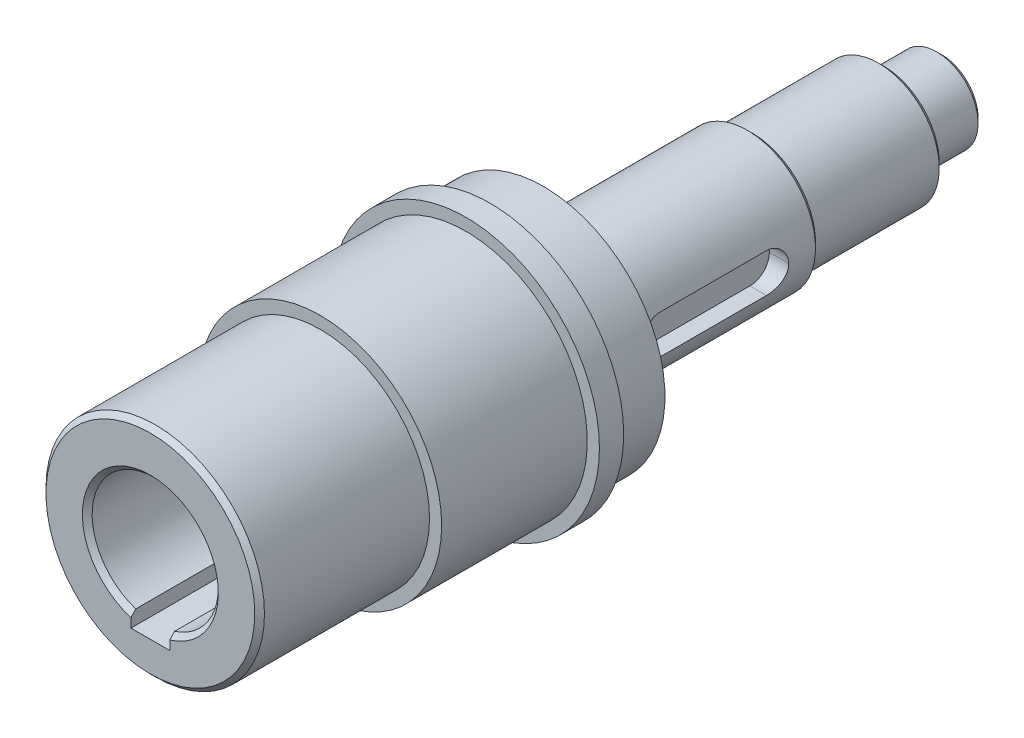
SolidWorks part; units mm, degrees
ref_plane "前视基准面" through (0, 0, 0) normal (0, 0, 1) x (1, 0, 0)
ref_plane "上视基准面" through (0, 0, 0) normal (0, 1, 0) x (1, 0, 0)
ref_plane "右视基准面" through (0, 0, 0) normal (1, 0, 0) x (0, 0, -1)
sketch "草图1" plane through (0, 0, 0) normal (0, 0, 1) x (1, 0, 0)
  circle A0 centre (0, 0) radius 25
  dimension "D1" = 50
extrude "凸台-拉伸1" add sketch "草图1" along normal blind 30
sketch "草图2" plane through (0, 0, 0) normal (0, 0, -1) x (-1, 0, 0)
  circle A0 centre (0, 0) radius 27.5
  dimension "D1" = 55
extrude "凸台-拉伸2" add sketch "草图2" along normal blind 5
sketch "草图3" plane through (0, 0, -5) normal (0, 0, -1) x (-1, 0, 0)
  circle A0 centre (0, 0) radius 25
  dimension "D1" = 50
extrude "凸台-拉伸3" add sketch "草图3" along normal blind 11
sketch "草图4" plane through (0, 0, -16) normal (0, 0, -1) x (-1, 0, 0)
  circle A0 centre (0, 0) radius 14
  dimension "D1" = 28
extrude "凸台-拉伸4" add sketch "草图4" along normal blind 43
sketch "草图5" plane through (0, 0, -59) normal (0, 0, -1) x (-1, 0, 0)
  circle A0 centre (0, 0) radius 12.5
  dimension "D1" = 25
extrude "凸台-拉伸5" add sketch "草图5" along normal blind 27
sketch "草图6" plane through (0, 0, -86) normal (0, 0, -1) x (-1, 0, 0)
  circle A0 centre (0, 0) radius 8.5
  dimension "D1" = 17
extrude "凸台-拉伸6" add sketch "草图6" along normal blind 12
sketch "草图7" plane through (0, 0, 0) normal (0, 1, 0) x (1, 0, 0)
  line L0 (14, 16) -> (14, 59) construction
  line L1 (14, 52.5) -> (10, 52.5)
  line L2 (14, 52.5) -> (14, 22.5)
  line L3 (14, 22.5) -> (10, 22.5)
  line L4 (10, 52.5) -> (10, 22.5)
  line L5 (14, 59) -> (-14, 59) construction
  dimension "D1" = 4
  dimension "D2" = 30
  dimension "D3" = 6.5
extrude "切除-拉伸1" cut sketch "草图7" against normal blind 4 and the other way blind 4
fillet "圆角1" radius 4 4 edges at (11.7082, 4, -22.5) (11.7082, -4, -22.5) (11.7082, -4, -52.5) (11.7082, 4, -52.5)
chamfer "倒角1" distance 1 angle 45 3 edges at (-8.5, 0, -98) (-12.5, 0, -86) (-14, 0, -59)
sketch "草图8" plane through (0, 0, 30) normal (0, 0, 1) x (1, 0, 0)
  circle A0 centre (0, 0) radius 22.5
  dimension "D1" = 45
extrude "凸台-拉伸7" add sketch "草图8" along normal blind 35
chamfer "倒角2" distance 1 angle 45 1 edges at (22.5, 0, 65)
sketch "草图9" plane through (0, 0, 65) normal (0, 0, 1) x (1, 0, 0)
  circle A0 centre (0, 0) radius 13
  dimension "D1" = 26
extrude "切除-拉伸2" cut sketch "草图9" against normal blind 40
chamfer "倒角3" distance 1 angle 45 1 edges at (13, 0, 65)
sketch "草图10" plane through (0, 0, 65) normal (0, 0, 1) x (1, 0, 0)
  line L0 (0, -13) -> (12.2731, -13) construction
  line L1 (-4, -13) -> (-4, -8.8816)
  line L3 (4, -13) -> (4, -15.3)
  line L4 (4, -15.3) -> (-4, -15.3)
  line L5 (-4, -13) -> (-4, -15.3)
  line L6 (-4, -8.8816) -> (4, -8.8816)
  line L7 (4, -8.8816) -> (4, -13)
  circle A0 centre (0, 0) radius 13 construction
  circle A1 centre (0, 0) radius 13 construction
  dimension "D1" = 2.3
  dimension "D2" = 8
  dimension "D3" = 4
extrude "切除-拉伸3" cut sketch "草图10" against normal blind 34
